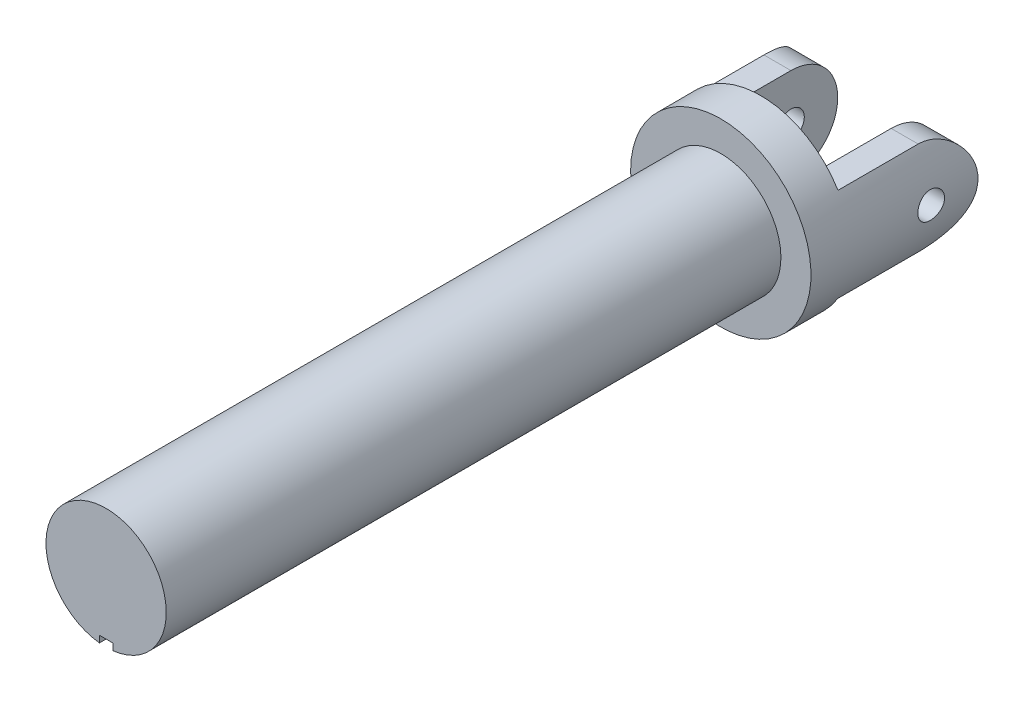
SolidWorks part; units mm, degrees
ref_plane "Front Plane" through (0, 0, 0) normal (0, 0, 1) x (1, 0, 0)
ref_plane "Top Plane" through (0, 0, 0) normal (0, 1, 0) x (1, 0, 0)
ref_plane "Right Plane" through (0, 0, 0) normal (1, 0, 0) x (0, 0, -1)
sketch "Sketch1" plane through (0, 0, 0) normal (0, 0, 1) x (1, 0, 0)
  circle A0 centre (0, 0) radius 4.5
  dimension "D1" = 9
extrude "Yoke" add sketch "Sketch1" along normal mid plane 46 contours A0
sketch "Sketch2" plane through (0, 0, -23) normal (0, 0, -1) x (-1, 0, 0)
  circle A0 centre (0, 0) radius 6.75
  dimension "D1" = 13.5
extrude "U Joint Base" add sketch "Sketch2" along normal blind 3
sketch "Sketch3" plane through (0, 0, -26) normal (0, 0, -1) x (-1, 0, 0)
  line L0 (-5.7717, 3.5) -> (-3.75, 3.5)
  line L1 (-3.75, 3.5) -> (-3.75, -3.5)
  line L2 (-3.75, -3.5) -> (-5.7717, -3.5)
  line L3 (3.75, -3.5) -> (3.75, 3.5)
  line L4 (3.75, 3.5) -> (5.7717, 3.5)
  line L5 (5.7717, -3.5) -> (3.75, -3.5)
  circle A0 centre (0, 0) radius 6.75 construction
  arc A1 (-5.7717, -3.5) -> (-5.7717, 3.5) centre (0, 0) cw
  arc A2 (5.7717, 3.5) -> (5.7717, -3.5) centre (0, 0) cw
  point P16 (0, 0)
  dimension "D2" = 7.5
  dimension "D3" = 7
  dimension "D1" = 2
extrude "U Joint Standups" add sketch "Sketch3" along normal blind 9.5
sketch "Sketch4" plane through (0, 0, 0) normal (1, 0, 0) x (0, 0, -1)
  line L0 (35.5, 3.5) -> (26, 3.5) construction
  line L1 (35.5, -3.5) -> (35.5, 3.5) construction
  line L2 (32, -3.5) -> (35.5, -3.5)
  line L3 (35.5, -3.5) -> (35.5, 0)
  line L4 (35.5, 0) -> (35.5, 3.5)
  line L5 (35.5, 3.5) -> (32, 3.5)
  line L6 (35.5, -3.5) -> (26, -3.5) construction
  arc A0 (35.5, 0) -> (32, 3.5) centre (32, 0) ccw
  arc A1 (32, -3.5) -> (35.5, 0) centre (32, 0) ccw
extrude "Standup Round" cut sketch "Sketch4" against normal through all both and the other way through all contours A1 L2 L3 | A0 L5 L4 region at (0, -2.7182, -34.7182)
sketch "Sketch5" plane through (0, 0, 0) normal (1, 0, 0) x (0, 0, -1)
  circle A0 centre (32, 0) radius 1
  dimension "D1" = 2
extrude "Ball Holes" cut sketch "Sketch5" against normal through all both and the other way through all
sketch "Sketch6" plane through (0, 0, 23) normal (0, 0, 1) x (1, 0, 0)
  line L0 (0.5, -4.4721) -> (0.5, -4.702)
  line L1 (-0.5, -4.4721) -> (-0.5, -3.9721)
  line L2 (-0.5, -3.9721) -> (0.5, -3.9721)
  line L3 (0.5, -3.9721) -> (0.5, -4.4721)
  line L4 (0.5, -4.702) -> (-0.5, -4.702)
  line L5 (-0.5, -4.702) -> (-0.5, -4.4721)
  circle A1 centre (0, 0) radius 4.5 construction
  circle A4 centre (0, 0) radius 4.5 construction
  point P4 (0.5, -4.4721)
  point P11 (-0.5, -4.4721)
  dimension "D1" = 0.5
  dimension "D2" = 1
  dimension "D3" = 0.5
extrude "Keyway" cut sketch "Sketch6" against normal blind 46 contours L4 L5 L1 L2 L3 L0
